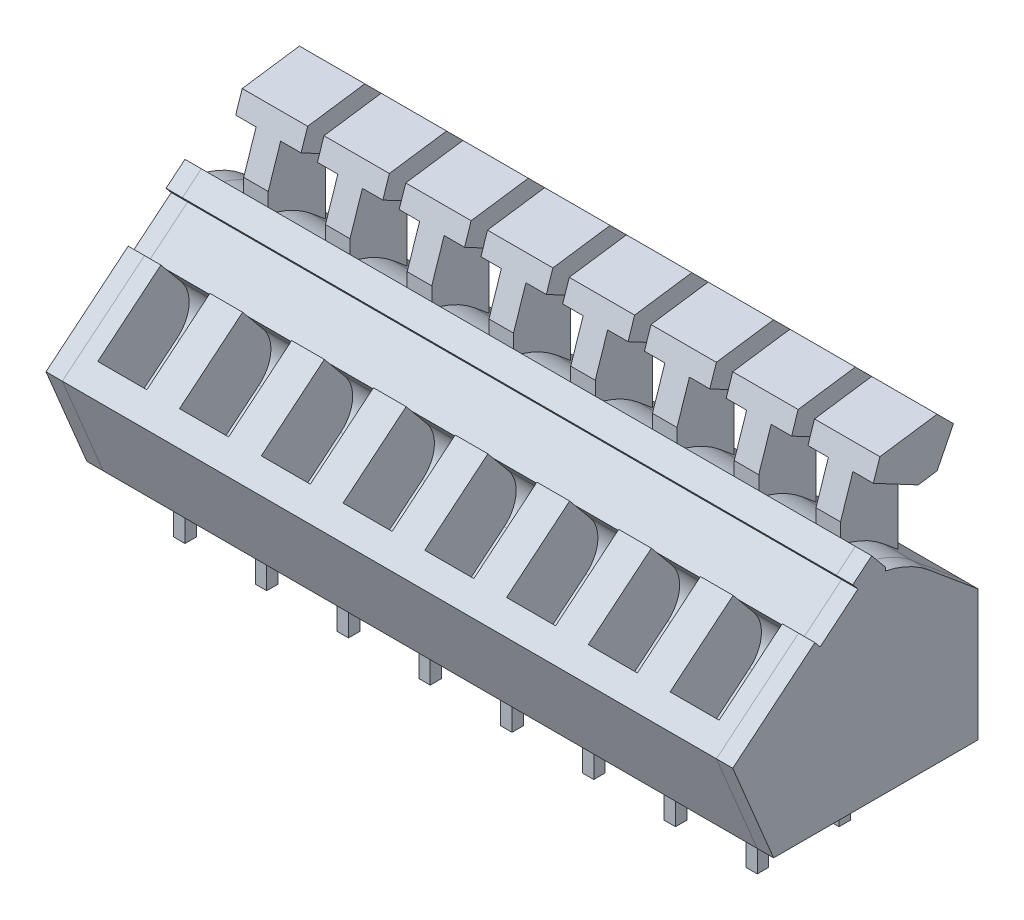
SolidWorks part; units mm, degrees
ref_plane "前视基准面" through (0, 0, 0) normal (0, 0, 1) x (1, 0, 0)
ref_plane "上视基准面" through (0, 0, 0) normal (0, 1, 0) x (1, 0, 0)
ref_plane "右视基准面" through (0, 0, 0) normal (1, 0, 0) x (0, 0, -1)
sketch "草图1" plane through (0, 0, 0) normal (1, 0, 0) x (0, 0, -1)
  line L0 (-6.25, 0) -> (6.25, 0)
  line L1 (6.25, 0) -> (6.25, 8)
  line L2 (6.25, 8) -> (3.25, 10.5)
  line L5 (0.5921, 11.9774) -> (-0.25, 13)
  line L6 (-0.25, 13) -> (-1.4079, 12.0464)
  line L7 (-8.75, 6) -> (-6.25, 0)
  line L8 (-0.25, 13) -> (15.8204, 13) construction
  line L9 (-1.4079, 12.0464) -> (-1.09, 11.6605)
  line L10 (-1.09, 11.6605) -> (-3.4058, 9.7534)
  line L11 (-3.4058, 9.7534) -> (-3.7237, 10.1393)
  line L12 (-3.7237, 10.1393) -> (-8.75, 6)
  line L13 (0.5921, 11.9774) -> (0.5921, 11.7774)
  arc A0 (0.5921, 11.7774) -> (3.25, 10.5) centre (-0.6151, 5.8618) cw
  point P4 (0, 0)
  dimension "D13" = 0.2
  dimension "D1" = 15
  dimension "D2" = 13
  dimension "D3" = 3
  dimension "D4" = 6.5
  dimension "D5" = 6
  dimension "D6" = 8
  dimension "D7" = 10.5
  dimension "D8" = 2
  dimension "D9" = 0.5
  dimension "D10" = 3
  dimension "D11" = 1.5
  dimension "D12" = 12.5
extrude "凸台-拉伸1" add sketch "草图1" along normal mid plane 5
sketch "草图3" plane through (0, 0, 0) normal (0, -1, 0) x (1, 0, 0)
  line L0 (2.5, -6.25) -> (-2.5, -6.25) construction
  line L1 (-0.35, 4.1) -> (0.35, 4.1)
  line L2 (-0.35, 4.1) -> (-0.35, 3.4)
  line L3 (-0.35, 3.4) -> (0.35, 3.4)
  line L4 (0.35, 4.1) -> (0.35, 3.4)
  line L5 (-0.35, 4.1) -> (0.35, 3.4) construction
  line L6 (-0.35, 3.4) -> (0.35, 4.1) construction
  line L7 (-0.35, -0.9) -> (0.35, -0.9)
  line L8 (-0.35, -0.9) -> (-0.35, -1.6)
  line L9 (-0.35, -1.6) -> (0.35, -1.6)
  line L10 (0.35, -0.9) -> (0.35, -1.6)
  line L11 (-0.35, -0.9) -> (0.35, -1.6) construction
  line L12 (-0.35, -1.6) -> (0.35, -0.9) construction
  point P0 (0, 3.75)
  point P5 (0, -1.25)
  dimension "D1" = 5
  dimension "D2" = 5
  dimension "D3" = 0.7
extrude "凸台-拉伸3" add sketch "草图3" along normal blind 3.5
sketch "草图4" plane through (0, 0, 0) normal (1, 0, 0) x (0, 0, -1)
  line L0 (0.5921, 9.7982) -> (0.5921, 13)
  line L2 (0.5921, 13) -> (1.75, 16.5)
  line L3 (1.75, 16.5) -> (5.25, 17)
  line L4 (5.25, 17) -> (6.25, 16)
  line L5 (-6.25, 0) -> (6.25, 0) construction
  line L6 (6.25, 16) -> (5.25, 14)
  line L7 (4.0921, 13.8346) -> (4.0921, 9.7982)
  line L8 (6.25, 8) -> (3.25, 10.5) construction
  line L9 (6.25, 0) -> (6.25, 8) construction
  line L11 (5.25, 14) -> (4.0921, 13.8346)
  line L12 (0.5921, 9.7982) -> (4.0921, 9.7982)
  line L13 (0.5921, 11.7774) -> (0.5921, 11.9774) construction
  line L15 (4.0921, 13.8346) -> (1.35, 15.2909)
  point P2 (4.0921, 13.7288)
  point P7 (0, 0)
  point P14 (1.4478, 15.5865)
  dimension "D1" = 3.5
  dimension "D2" = 3.5
  dimension "D3" = 5.5
  dimension "D4" = 2
  dimension "D5" = 14
  dimension "D6" = 17
  dimension "D7" = 16
  dimension "D8" = 1.6
extrude "凸台-拉伸7" add sketch "草图4" along normal mid plane 1.5 contours L7 L15 L2 L0 L12 region at (0, 12.1634, -2.3195)
extrude "凸台-拉伸9" add sketch "草图4<3>" along normal mid plane 4 contours L15 L11 L6 L4 L3 L2 region at (0, 15.5171, -3.9198)
sketch "草图4<3>" plane through (0, 0, 0) normal (1, 0, 0) x (0, 0, -1) same geometry as "草图4"
sketch "草图5" plane through (0, 0, 0) normal (1, 0, 0) x (0, 0, -1)
  line L0 (-3.4058, 9.7534) -> (-1.1809, 7.0516)
  line L1 (-1.1809, 7.0516) -> (-5.0405, 3.8731)
  line L2 (-5.0405, 3.8731) -> (-7.5833, 6.9608)
  line L3 (-3.7237, 10.1393) -> (-8.75, 6) construction
  line L4 (-3.4058, 9.7534) -> (-3.7237, 10.1393) construction
  line L5 (-7.5833, 6.9608) -> (-3.7237, 10.1393)
  line L6 (-3.7237, 10.1393) -> (-3.4058, 9.7534)
  dimension "D1" = 4
  dimension "D2" = 5
extrude "切除-拉伸1" cut sketch "草图5" against normal mid plane 3
fillet "圆角1" radius 2 1 edges at (0, 7.0516, 1.1809)
pattern_linear "阵列(线性)2" count 8 spacing 5 along (1, 0, 0) of "凸台-拉伸1", "凸台-拉伸3", "凸台-拉伸7", "切除-拉伸1", "圆角1", "凸台-拉伸9"
sketch "草图2" plane through (-2.5, 0, 0) normal (1, 0, 0) x (0, 0, -1)
  line L12 (-1.4079, 12.0464) -> (-1.09, 11.6605)
  line L13 (-1.09, 11.6605) -> (-3.4058, 9.7534)
  line L14 (-3.4058, 9.7534) -> (-3.7237, 10.1393)
  line L15 (-3.7237, 10.1393) -> (-8.75, 6)
  line L16 (-8.75, 6) -> (-6.25, 0)
  line L17 (-6.25, 0) -> (6.25, 0)
  line L18 (6.25, 0) -> (6.25, 8)
  line L19 (6.25, 8) -> (3.25, 10.5)
  line L21 (0.5921, 11.7774) -> (0.5921, 11.9774)
  line L22 (0.5921, 11.9774) -> (-0.25, 13)
  line L23 (-0.25, 13) -> (-1.4079, 12.0464)
  line L24 (-1.4079, 12.0464) -> (-1.09, 11.6605)
  line L25 (-1.09, 11.6605) -> (-3.4058, 9.7534)
  line L26 (-3.4058, 9.7534) -> (-3.7237, 10.1393)
  line L27 (-3.7237, 10.1393) -> (-8.75, 6)
  line L28 (-8.75, 6) -> (-6.25, 0)
  line L29 (-6.25, 0) -> (6.25, 0)
  line L30 (6.25, 0) -> (6.25, 8)
  line L31 (6.25, 8) -> (3.25, 10.5)
  line L33 (0.5921, 11.7774) -> (0.5921, 11.9774)
  line L34 (0.5921, 11.9774) -> (-0.25, 13)
  line L35 (-0.25, 13) -> (-1.4079, 12.0464)
  arc A1 (3.25, 10.5) -> (0.5921, 11.7774) centre (-0.6151, 5.8618) ccw
  arc A2 (3.25, 10.5) -> (0.5921, 11.7774) centre (-0.6151, 5.8618) ccw
  dimension "D1" = 0
extrude "两侧加厚" add sketch "草图2" against normal blind 1 separate body
ref_plane "基准面1" through (37.5, 0, 0) normal (1, 0, 0) x (0, 0, -1)
sketch "草图6" plane through (37.5, 0, 0) normal (1, 0, 0) x (0, 0, -1)
  line L12 (-1.4079, 12.0464) -> (-1.09, 11.6605)
  line L13 (-1.09, 11.6605) -> (-3.4058, 9.7534)
  line L14 (-3.4058, 9.7534) -> (-3.7237, 10.1393)
  line L15 (-3.7237, 10.1393) -> (-8.75, 6)
  line L16 (-8.75, 6) -> (-6.25, 0)
  line L17 (-6.25, 0) -> (6.25, 0)
  line L18 (6.25, 0) -> (6.25, 8)
  line L19 (6.25, 8) -> (3.25, 10.5)
  line L21 (0.5921, 11.7774) -> (0.5921, 11.9774)
  line L22 (0.5921, 11.9774) -> (-0.25, 13)
  line L23 (-0.25, 13) -> (-1.4079, 12.0464)
  line L24 (-1.4079, 12.0464) -> (-1.09, 11.6605)
  line L25 (-1.09, 11.6605) -> (-3.4058, 9.7534)
  line L26 (-3.4058, 9.7534) -> (-3.7237, 10.1393)
  line L27 (-3.7237, 10.1393) -> (-8.75, 6)
  line L28 (-8.75, 6) -> (-6.25, 0)
  line L29 (-6.25, 0) -> (6.25, 0)
  line L30 (6.25, 0) -> (6.25, 8)
  line L31 (6.25, 8) -> (3.25, 10.5)
  line L33 (0.5921, 11.7774) -> (0.5921, 11.9774)
  line L34 (0.5921, 11.9774) -> (-0.25, 13)
  line L35 (-0.25, 13) -> (-1.4079, 12.0464)
  arc A1 (3.25, 10.5) -> (0.5921, 11.7774) centre (-0.6151, 5.8618) ccw
  arc A2 (3.25, 10.5) -> (0.5921, 11.7774) centre (-0.6151, 5.8618) ccw
  dimension "D1" = 0
extrude "凸台-拉伸8" add sketch "草图6" along normal blind 1 separate body
ref_plane "中心面" through (17.5, 0, 0) normal (1, 0, 0) x (0, 0, -1)
